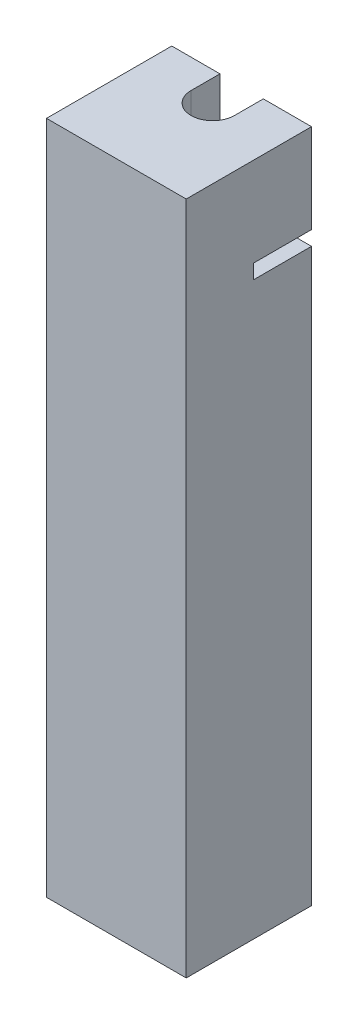
SolidWorks part; units mm, degrees
ref_plane "Front Plane" through (0, 0, 0) normal (0, 0, 1) x (1, 0, 0)
ref_plane "Top Plane" through (0, 0, 0) normal (0, 1, 0) x (1, 0, 0)
ref_plane "Right Plane" through (0, 0, 0) normal (1, 0, 0) x (0, 0, -1)
sketch "Sketch1" plane through (0, 0, 0) normal (0, 1, 0) x (1, 0, 0)
  line L0 (-7.25, 0) -> (7.25, 0) construction
  line L1 (-7.25, 3) -> (-2.25, 3)
  line L2 (-7.25, 3) -> (-7.25, -10)
  line L3 (-7.25, -10) -> (7.25, -10)
  line L4 (7.25, 3) -> (7.25, -10)
  line L5 (-2.25, 0) -> (-2.25, 3)
  line L6 (2.25, 0) -> (2.25, 3)
  line L7 (-2.25, 3) -> (2.25, 3) construction
  line L8 (2.25, 3) -> (7.25, 3)
  arc A0 (-2.25, 0) -> (2.25, 0) centre (0, 0) ccw
  arc A1 (2.25, 0) -> (-2.25, 0) centre (0, 0) ccw construction
  point P13 (0, 0)
  dimension "D1" = 4.5
  dimension "D2" = 5
  dimension "D3" = 3
  dimension "D4" = 10
extrude "Boss-Extrude1" add sketch "Sketch1" along normal mid plane 70
sketch "Sketch2" plane through (0, 0, -3) normal (0, 0, -1) x (-1, 0, 0)
  line L0 (7.25, 35) -> (7.25, -35) construction
  line L1 (-7.25, -35) -> (7.25, -35)
  line L2 (-7.25, -35) -> (-7.25, -25.75)
  line L3 (-7.25, -25.75) -> (7.25, -25.75)
  line L4 (7.25, -35) -> (7.25, -25.75)
  line L5 (-7.25, 35) -> (-7.25, -35) construction
  line L6 (-7.25, 24.25) -> (7.25, 24.25)
  line L7 (-7.25, 24.25) -> (-7.25, 25.75)
  line L8 (-7.25, 25.75) -> (7.25, 25.75)
  line L9 (7.25, 24.25) -> (7.25, 25.75)
  line L10 (-7.25, 25.75) -> (-7.25, 35) construction
  line M6 (-7.25, -35) -> (-2.25, -35)
  line M7 (-2.25, -35) -> (-2.25, 35)
  line M9 (-7.25, 35) -> (-7.25, -35)
  dimension "D1" = 1.5
  dimension "D2" = 50
extrude "Cut-Extrude1" cut sketch "Sketch2" against normal blind 6 contours L6 L9 L8 M7 | L8 L6 M9 M7 region at (4.75, 25, -3) region at (-2.5, 25, -3)
extrude "Boss-Extrude2" add sketch "Sketch2<3>" against normal through all contours L1 L4 L3 M7 | L3 M9 M6 M7 region at (4.75, -30.375, -3) region at (-2.5, -30.375, -3)
sketch "Sketch2<3>" plane through (0, 0, -3) normal (0, 0, -1) x (-1, 0, 0) same geometry as "Sketch2"
sketch "Sketch3" plane through (0, -25.75, 0) normal (0, 1, 0) x (1, 0, 0)
  line L3 (2.25, 0) -> (2.25, 3)
  line L4 (2.25, 3) -> (-2.25, 3)
  line L5 (-2.25, 3) -> (-2.25, 0)
  line L6 (2.25, 0) -> (2.25, 3)
  line L7 (2.25, 3) -> (-2.25, 3)
  line L8 (-2.25, 3) -> (-2.25, 0)
  arc A0 (2.25, 0) -> (-2.25, 0) centre (0, 0) ccw
  arc A1 (-2.25, 0) -> (2.25, 0) centre (0, 0) ccw construction
  arc A3 (-2.25, 0) -> (2.25, 0) centre (0, 0) ccw
  dimension "D1" = 0
extrude "Boss-Extrude3" add sketch "Sketch3" along normal blind 3
equation "\"length\" = 50mm"
equation "\"D1@Boss-Extrude1\"=\"length\"+20"
equation "\"D2@Sketch2\"=\"length\""
